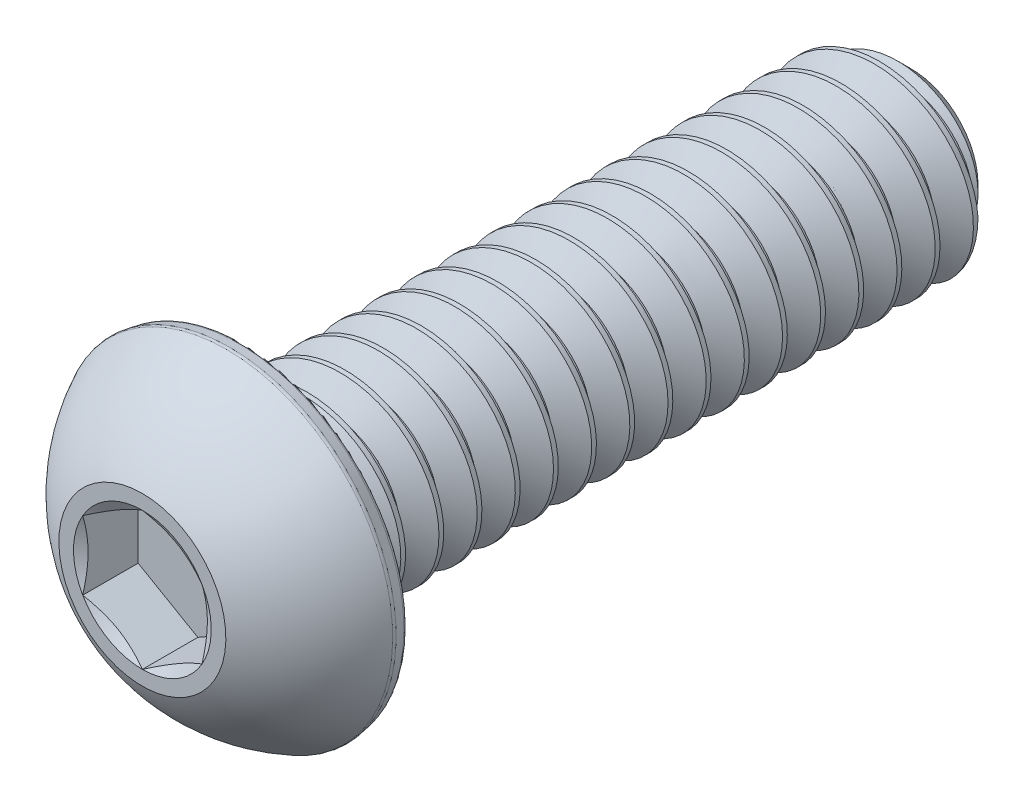
SolidWorks part; units mm, degrees
material "Plain Carbon Steel"
ref_plane "Front Plane" through (0, 0, 0) normal (0, 0, 1) x (1, 0, 0)
ref_plane "Top Plane" through (0, 0, 0) normal (0, 1, 0) x (1, 0, 0)
ref_plane "Right Plane" through (0, 0, 0) normal (1, 0, 0) x (0, 0, -1)
sketch "Sketch1" plane through (0, 0, 0) normal (1, 0, 0) x (0, 0, -1)
  line L0 (-12.7889, 0) -> (12.7889, 0) construction
  line L1 (-12.7889, 0) -> (-12.7889, 5.5499)
  line L2 (-12.7889, 5.5499) -> (-9.4361, 5.5499)
  line L3 (-9.4361, 5.5499) -> (-9.4361, 3.175)
  line L4 (-9.4361, 3.175) -> (12.7889, 3.175)
  line L5 (12.7889, 3.175) -> (12.7889, 0)
  point P2 (0, 0)
  point P4 (11.5189, 0)
  point P9 (10.8839, 3.175)
  point P10 (10.8839, -3.175)
  point P11 (12.7889, -3.175)
  point P15 (-10.9449, 0)
  dimension "Head Height" = 3.3528
  dimension "Head Diameter" = 11.0998
  dimension "Length" = 22.225
  dimension "Screw Size Decimal Equivalent" = 6.35
  dimension "Thread Pitch" = 1.27
  dimension "D1" = 1.905
  dimension "D2" = 1.844
sketch "Sketch2" plane through (0, 0, 0) normal (0, 0, 1) x (1, 0, 0)
  line L0 (0, 3.175) -> (0, 0) construction
  line L1 (0, 2.2914) -> (-1.9844, 1.1457)
  line L2 (-1.9844, 1.1457) -> (-1.9844, -1.1457)
  line L3 (-1.9844, -1.1457) -> (0, -2.2914)
  line L4 (0, -2.2914) -> (1.9844, -1.1457)
  line L5 (1.9844, -1.1457) -> (1.9844, 1.1457)
  line L6 (1.9844, 1.1457) -> (0, 2.2914)
  circle A0 centre (0, 0) radius 1.9844 construction
  circle A1 centre (0, 0) radius 2.7781
  point P10 (0, 2.7781)
  dimension "D1" = 5.5563
  dimension "Drive Size" = 3.9688
sketch "Sketch3" plane through (0, 0, 0) normal (1, 0, 0) x (0, 0, -1)
  line L0 (-12.7889, 0) -> (-12.7889, 2.7781)
  line L1 (-12.7889, 0) -> (-12.7889, 5.5499) construction
  line L2 (-12.7889, 5.5499) -> (-9.4361, 5.5499) construction
  line L3 (-9.939, 5.5499) -> (-9.4361, 5.4612)
  line L4 (-9.4361, 5.5499) -> (-9.4361, 3.175) construction
  line L5 (-9.4361, 5.4612) -> (-9.4361, 3.175)
  line L6 (-12.7889, 0) -> (12.7889, 0) construction
  line L7 (-12.7889, 0) -> (12.7889, 0)
  line L8 (12.7889, 0) -> (12.7889, 2.2225)
  line L9 (12.7889, 3.175) -> (12.7889, 0) construction
  line L10 (12.7889, 2.2225) -> (11.8364, 3.175)
  line L11 (-9.4361, 3.175) -> (12.7889, 3.175) construction
  line L12 (11.8364, 3.175) -> (-9.4361, 3.175)
  arc A0 (-12.7889, 2.7781) -> (-9.939, 5.5499) centre (-7.3141, 0) cw
  dimension "D1" = 0.5029
  dimension "D2" = 10
  dimension "D3" = 45
  dimension "D4" = 0.9525
revolve "Revolve1" add sketch "Sketch3" angle 360 about L7
sketch "Sketch4" plane through (0, 0, 12.7889) normal (0, 0, 1) x (1, 0, 0)
  line L0 (-1.9844, -1.1457) -> (0, -2.2914) construction
  line L1 (-1.9844, 1.1457) -> (-1.9844, -1.1457) construction
  line L2 (0, 2.2914) -> (-1.9844, 1.1457) construction
  line L3 (1.9844, 1.1457) -> (0, 2.2914) construction
  line L4 (1.9844, -1.1457) -> (1.9844, 1.1457) construction
  line L5 (0, -2.2914) -> (1.9844, -1.1457) construction
  line L6 (-1.9844, -1.1457) -> (0, -2.2914)
  line L7 (-1.9844, 1.1457) -> (-1.9844, -1.1457)
  line L8 (0, 2.2914) -> (-1.9844, 1.1457)
  line L9 (1.9844, 1.1457) -> (0, 2.2914)
  line L10 (1.9844, -1.1457) -> (1.9844, 1.1457)
  line L11 (0, -2.2914) -> (1.9844, -1.1457)
extrude "Cut-Extrude1" cut sketch "Sketch4" against normal up to vertex (1.844 mm away) up to point (0, 0, 10.9449)
sketch "Sketch5" plane through (0, 0, 12.7889) normal (0, 0, 1) x (1, 0, 0)
  circle A0 centre (0, 0) radius 2.2914
extrude "Cut-Extrude2" cut sketch "Sketch5" against normal up to vertex (1.844 mm away) draft 60 up to point (0, 0, 10.9449)
fillet "Fillet1" radius 0.1676 2 edges at (5.5499, 0, 9.939) (5.4612, 0, 9.4361)
split "Split1" bodies to split 106 resulting bodies 107 108 split by face at (5.3206, 0, 9.4361)
sketch "Sketch6" plane through (0, 0, -12.7889) normal (0, 0, -1) x (-1, 0, 0)
  circle A0 centre (0, 0) radius 3.175 construction
  circle A1 centre (0, 0) radius 3.175
curve "Helix/Spiral1" pitch 1.27 height 23.495 radius 3.175 centre (0, 0, -12.7889) axis (0, 0, 1) start towards (0, 1, 0)
sketch "Sketch7" plane through (0, 0, 0) normal (1, 0, 0) x (0, 0, -1)
  line L0 (12.7095, 3.3125) -> (13.3445, 2.2126) construction
  line L1 (13.3445, 2.2126) -> (13.9795, 3.3125) construction
  line L2 (13.9795, 3.3125) -> (12.7095, 3.3125) construction
  line L3 (12.7492, 3.2437) -> (13.9398, 3.2437)
  line L4 (13.9398, 3.2437) -> (13.4239, 2.3501)
  line L5 (13.4239, 2.3501) -> (13.2652, 2.3501)
  line L6 (13.2652, 2.3501) -> (12.7492, 3.2437)
  line L7 (13.3445, 2.3501) -> (13.3445, 2.2126) construction
  line L8 (12.7889, 3.175) -> (13.9002, 3.175) construction
  line L9 (13.3445, 3.3125) -> (13.3445, 3.175) construction
  point P12 (13.3445, 3.2437)
  dimension "D2" = 0.1588
sweep "Cut-Sweep1" cut profiles "Sketch7" path "Helix/Spiral1" align with end faces yes
sketch "Sketch8" plane through (0, 0, 9.4361) normal (0, 0, -1) x (-1, 0, 0)
  circle A0 centre (0, 0) radius 3.3125
extrude "Boss-Extrude1" add sketch "Sketch8" along normal up to vertex (20.32 mm away) draft 45 up to point (0, 3.175, -10.8839)
equation "\"D1@Sketch1\"=\"Thread Pitch@Sketch1\"*1.5"
equation "\"D2@Sketch1\"=0.55*\"Head Height@Sketch1\""
equation "\"D1@Sketch2\"=\"Drive Size@Sketch2\"*1.4"
equation "\"D1@Sketch3\"=0.15*\"Head Height@Sketch1\""
equation "\"D4@Sketch3\"=0.75*\"Thread Pitch@Sketch1\""
equation "\"D1@Fillet1\"=.05*\"Head Height@Sketch1\""
equation "\"D4@Helix/Spiral1\"=\"Thread Pitch@Sketch1\""
equation "\"D3@Helix/Spiral1\"=\"Length@Sketch1\"+\"Thread Pitch@Sketch1\""
equation "\"D2@Sketch7\"=\"D1@Sketch7\"/8"
equation "\"D1@Sketch7\"=\"Thread Pitch@Sketch1\""
